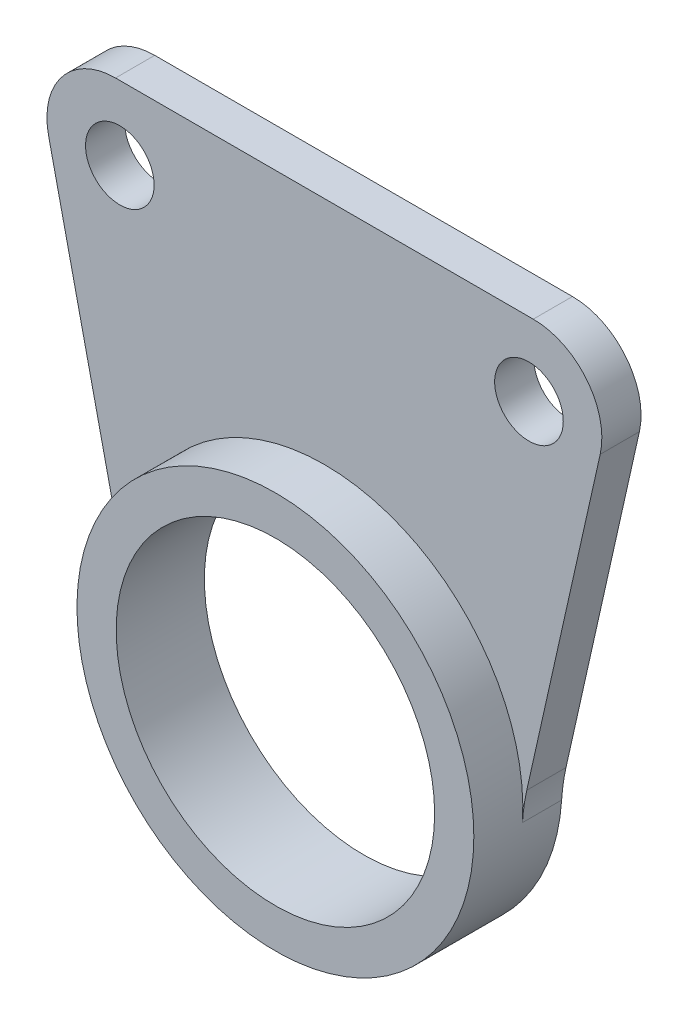
SolidWorks part; units mm, degrees
ref_plane "Plan de face" through (0, 0, 0) normal (0, 0, 1) x (1, 0, 0)
ref_plane "Plan de dessus" through (0, 0, 0) normal (0, 1, 0) x (1, 0, 0)
ref_plane "Plan de droite" through (0, 0, 0) normal (1, 0, 0) x (0, 0, -1)
sketch "Esquisse1" plane through (0, 0, 0) normal (0, 0, 1) x (1, 0, 0)
  line L0 (-10.4375, 18.125) -> (10.4375, 18.125) construction
  line L1 (-10.125, 0) -> (-15.028, 21.875)
  line L2 (-15.028, 21.875) -> (15.028, 21.875)
  line L3 (15.028, 21.875) -> (10.125, 0)
  line L4 (-10.4375, 18.125) -> (-10.4375, 21.875) construction
  line L5 (-10.4375, 18.125) -> (-14.1875, 18.125) construction
  line L6 (0, 0) -> (0, 18.125) construction
  circle A0 centre (0, 0) radius 8.125
  circle A1 centre (0, 0) radius 10.125
  circle A2 centre (-10.4375, 18.125) radius 1.75
  circle A3 centre (10.4375, 18.125) radius 1.75
  point P7 (0, 18.125)
  point P12 (0, 21.875)
  dimension "D1" = 16.25
  dimension "D4" = 3.5
  dimension "D3" = 20.875
  dimension "D5" = 3.75
  dimension "D6" = 18.125
  dimension "D2" = 2
extrude "Boss.-Extru.1" add sketch "Esquisse1" along normal blind 4.5 contours A1 A0 region at (0, 9.8386, 0)
extrude "Boss.-Extru.2" add sketch "Esquisse1<3>" along normal blind 2 contours A1 L3 L2 L1 A3 A2 region at (0, 14.511, 0)
sketch "Esquisse1<3>" plane through (0, 0, 0) normal (0, 0, 1) x (1, 0, 0) same geometry as "Esquisse1"
fillet "Congé1" radius 3.5 2 edges at (15.028, 21.875, 1) (-15.028, 21.875, 1)
fillet "Congé2" radius 10 2 edges at (10.125, 0, 1) (-10.125, 0, 1)
